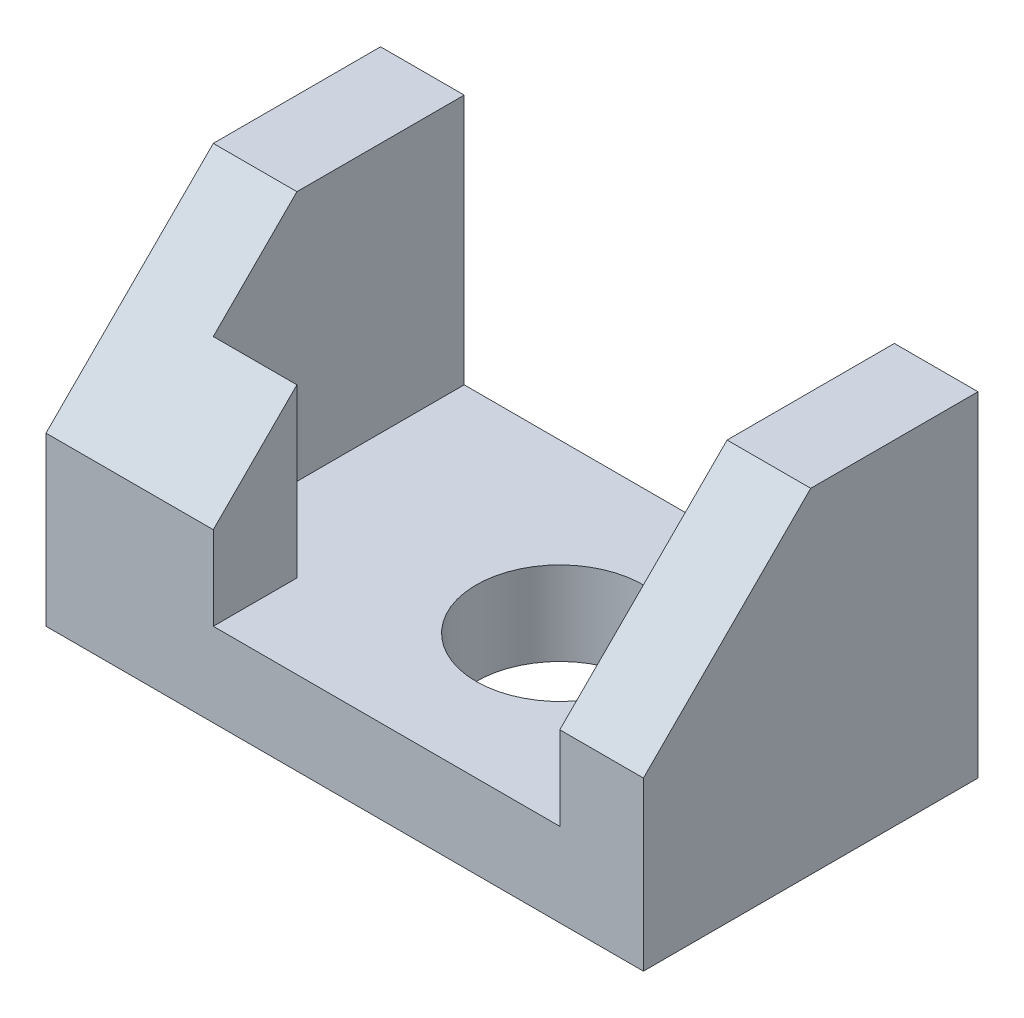
SolidWorks part; units mm, degrees
ref_plane "Front Plane" through (0, 0, 0) normal (0, 0, 1) x (1, 0, 0)
ref_plane "Top Plane" through (0, 0, 0) normal (0, 1, 0) x (1, 0, 0)
ref_plane "Right Plane" through (0, 0, 0) normal (1, 0, 0) x (0, 0, -1)
sketch "Sketch1" plane through (0, 0, 0) normal (0, 1, 0) x (1, 0, 0)
  line L0 (18, 14) -> (18, -14)
  line L1 (-25, -14) -> (25, -14)
  line L2 (-25, -14) -> (-25, 14)
  line L3 (-25, 14) -> (25, 14)
  line L4 (25, -14) -> (25, 14)
  line L5 (-25, -14) -> (25, 14) construction
  line L6 (-25, 14) -> (25, -14) construction
  line L7 (-18, 14) -> (-18, -7)
  line L8 (-18, -7) -> (-11, -7)
  line L9 (-11, -7) -> (-11, -14)
  circle A0 centre (4, 0) radius 7
  point P0 (0, 0)
  dimension "D3" = 14
  dimension "D1" = 50
  dimension "D2" = 28
  dimension "D4" = 14
  dimension "D5" = 7
  dimension "D6" = 14
  dimension "D7" = 7
  dimension "D8" = 7
  dimension "D9" = 14
extrude "Boss-Extrude1" add sketch "Sketch1" along normal blind 7 contours L8 L9 L1 L0 L3 L7 A0 region at (17.5439, 0, 0)
extrude "Boss-Extrude2" add sketch "Sketch1<3>" along normal blind 28 contours L9 L8 L7 L3 L2 L1 | L1 L4 L3 L0 region at (21.5, 0, 0) region at (-20.1, 0, 2.1)
sketch "Sketch1<3>" plane through (0, 0, 0) normal (0, 1, 0) x (1, 0, 0) same geometry as "Sketch1"
chamfer "Chamfer1" distance 14 2 edges at (-18, 28, 14) (21.5, 28, 14)
